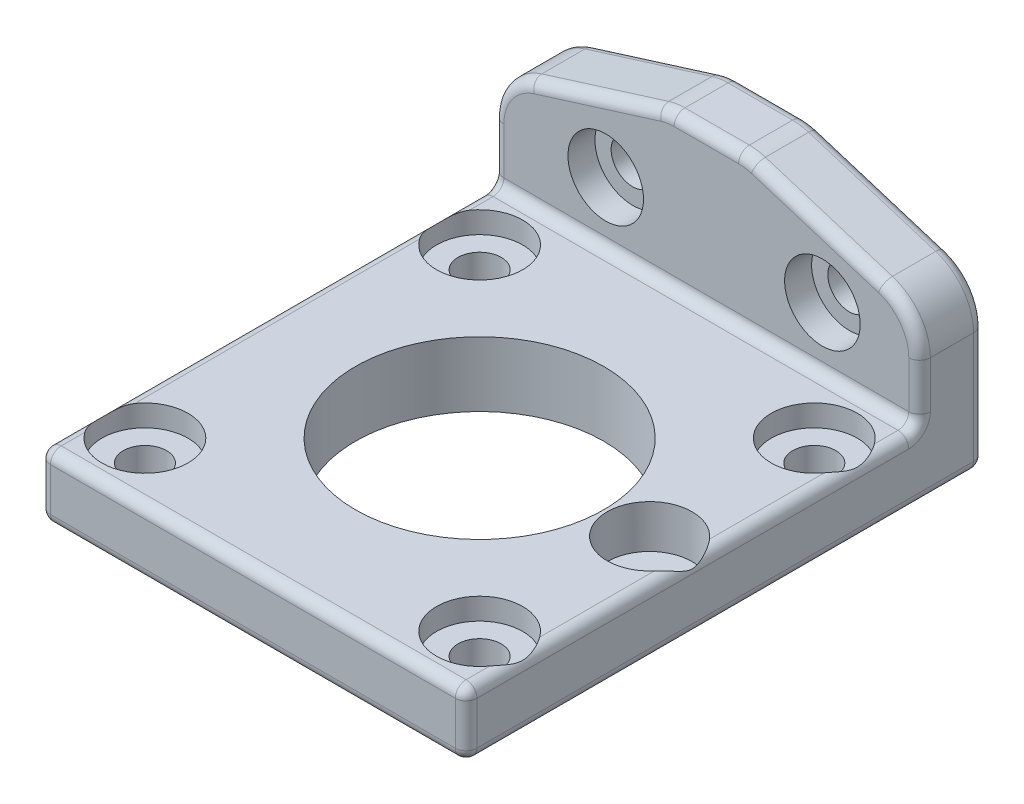
SolidWorks part; units mm, degrees
ref_plane "Front Plane" through (0, 0, 0) normal (0, 0, 1) x (1, 0, 0)
ref_plane "Top Plane" through (0, 0, 0) normal (0, 1, 0) x (1, 0, 0)
ref_plane "Right Plane" through (0, 0, 0) normal (1, 0, 0) x (0, 0, -1)
sketch "Sketch1" plane through (0, 0, 0) normal (0, 1, 0) x (1, 0, 0)
  line L1 (-19.75, 21) -> (19.75, 21)
  line L2 (-19.75, 21) -> (-19.75, -21)
  line L3 (-19.75, -21) -> (19.75, -21)
  line L4 (19.75, 21) -> (19.75, -21)
  line L5 (-19.75, 21) -> (19.75, -21) construction
  line L6 (-19.75, -21) -> (19.75, 21) construction
  point P0 (0, 0)
  dimension "D1" = 39.5
  dimension "D2" = 42
extrude "Boss-Extrude1" add sketch "Sketch1" along normal blind 6
sketch "Sketch3" plane through (0, 6, 0) normal (0, 1, 0) x (1, 0, 0)
  line L0 (0, -15.5) -> (0, 15.5) construction
  line L1 (-15.5, 0) -> (15.5, 0) construction
  line L2 (-15.5, 15.5) -> (15.5, 15.5) construction
  line L3 (15.5, 15.5) -> (15.5, -15.5) construction
  line L4 (15.5, -15.5) -> (-15.5, -15.5) construction
  line L5 (-15.5, -15.5) -> (-15.5, 15.5) construction
  circle A0 centre (-15.5, 15.5) radius 3.9905
  circle A1 centre (15.5, 15.5) radius 3.9905
  circle A2 centre (-15.5, -15.5) radius 3.9905
  circle A3 centre (15.5, -15.5) radius 3.9905
  point P12 (0, 0)
  point P16 (0, 0)
  point P17 (0, 15.5)
  point P20 (15.5, 0)
  dimension "D1" = 7.981
  dimension "D2" = 31
  dimension "D3" = 31
extrude "Cut-Extrude1" cut sketch "Sketch3" against normal blind 2
sketch "Sketch4" plane through (0, 6, 0) normal (0, 1, 0) x (1, 0, 0)
  circle A0 centre (0, 0) radius 11.5
  circle A1 centre (15.5, 15.5) radius 2
  circle A2 centre (-15.5, 15.5) radius 2
  circle A3 centre (-15.5, -15.5) radius 2
  circle A4 centre (15.5, -15.5) radius 2
  dimension "D1" = 4
  dimension "D2" = 23
extrude "Cut-Extrude2" cut sketch "Sketch4" against normal through all
sketch "Sketch5" plane through (0, 0, -21) normal (0, 0, -1) x (-1, 0, 0)
  line L0 (0, 7.5) -> (0, 17.375) construction
  line L2 (-19.75, 15) -> (-19.75, 0)
  line L3 (-19.75, 0) -> (19.75, 0)
  line L4 (19.75, 15) -> (19.75, 0)
  line L5 (-19.75, 15) -> (19.75, 0) construction
  line L6 (-19.75, 0) -> (19.75, 15) construction
  line L7 (-3.75, 20) -> (3.75, 20)
  line L11 (19.75, 15) -> (-19.75, 15) construction
  line L13 (3.75, 20) -> (19.75, 15)
  line L14 (-3.75, 20) -> (-19.75, 15)
  point P0 (0, 7.5)
  point P6 (0, 27.5)
  dimension "D1" = 20
  dimension "D2" = 15
  dimension "D3" = 16
  dimension "D4" = 16
extrude "Boss-Extrude2" add sketch "Sketch5" along normal blind 6
sketch "Sketch6" plane through (0, 0, -21) normal (0, 0, 1) x (1, 0, 0)
  line L0 (-9.32, 11.75) -> (10.75, 11.75) construction
  line L1 (-19.75, 6.845) -> (0.715, 6.845) construction
  line L2 (-19.75, 6) -> (-19.75, 15) construction
  line L3 (0.715, 6.845) -> (0.715, 11.75) construction
  circle A0 centre (-9.32, 11.75) radius 3.5
  circle A1 centre (10.75, 11.75) radius 3.5
  dimension "D1" = 7
  dimension "D2" = 7
  dimension "D3" = 20.465
  dimension "D4" = 20.07
  dimension "D5" = 11.75
extrude "Cut-Extrude3" cut sketch "Sketch6" against normal blind 2.5
sketch "Sketch7" plane through (0, 0, -21) normal (0, 0, 1) x (1, 0, 0)
  circle A0 centre (-9.32, 11.75) radius 2
  circle A1 centre (10.75, 11.75) radius 2
  dimension "D1" = 4
extrude "Cut-Extrude4" cut sketch "Sketch7" against normal through all
fillet "Fillet1" radius 5 4 edges at (19.75, 15, -24) (3.75, 20, -24) (-3.75, 20, -24) (-19.75, 15, -24)
sketch "Sketch8" plane through (0, 6, 0) normal (0, 1, 0) x (1, 0, 0)
  line L0 (0, 0) -> (15.75, 0) construction
  circle A0 centre (15.75, 0) radius 3.9365
  dimension "D1" = 7.873
  dimension "D2" = 15.75
extrude "Cut-Extrude5" cut sketch "Sketch8" against normal blind 4
fillet "Fillet2" radius 1 28 edges at (19.75, 6, 0) (19.75, 8.662, -21) (18.7785, 14.2857, -21) (10.3598, 17.9344, -21) (3.7413, 19.9428, -21) (0, 20, -21) (-3.7413, 19.9428, -21) (-10.3598, 17.9344, -21) (-18.7785, 14.2857, -21) (-19.75, 8.662, -21) (-19.75, 5.662, -27) (-18.7785, 14.2857, -27) (-10.3598, 17.9344, -27) (-3.7413, 19.9428, -27) (0, 20, -27) (3.7413, 19.9428, -27) (10.3598, 17.9344, -27) (18.7785, 14.2857, -27) (19.75, 5.662, -27) (0, 0, -27) (19.75, 0, -3) (0, 0, 21) (-19.75, 0, -3) (0, 6, 21) (-19.75, 6, 0) (0, 6, -21) (19.75, 3, 21) (-19.75, 3, 21)
